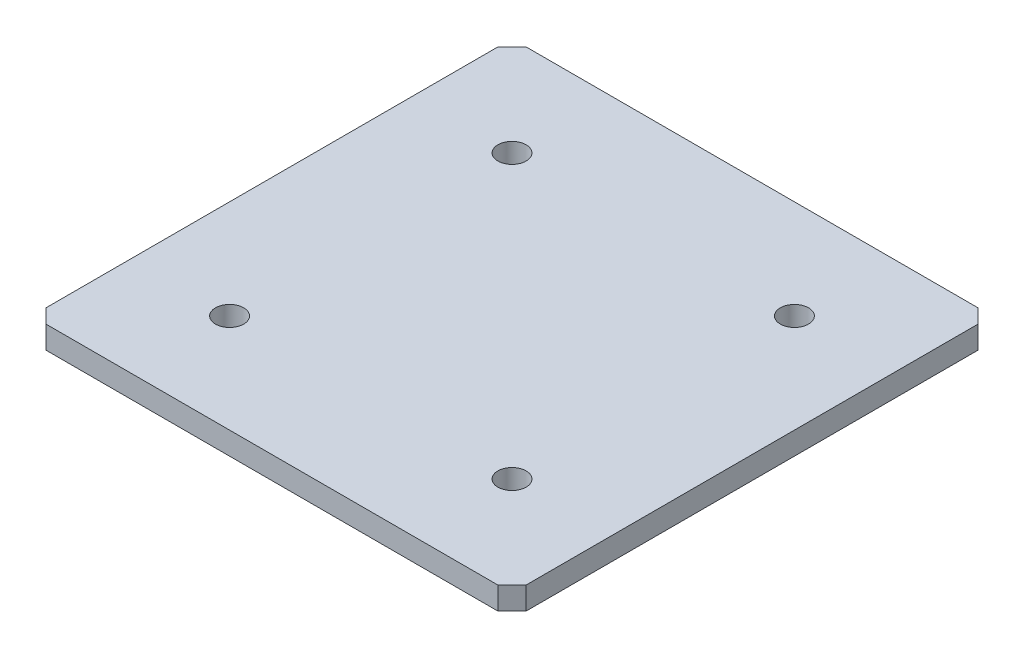
SolidWorks part; units mm, degrees
material "AU4G - 2017A"
ref_plane "Plan de face" through (0, 0, 0) normal (0, 0, 1) x (1, 0, 0)
ref_plane "Plan de dessus" through (0, 0, 0) normal (0, 1, 0) x (1, 0, 0)
ref_plane "Plan de droite" through (0, 0, 0) normal (1, 0, 0) x (0, 0, -1)
sketch "Sketch1" plane through (0, 0, 0) normal (0, 1, 0) x (1, 0, 0)
  line L0 (-85, -85) -> (85, 85) construction
  line L1 (-85, -85) -> (85, -85)
  line L2 (-85, -85) -> (-85, 85)
  line L3 (-85, 85) -> (85, 85)
  line L4 (85, -85) -> (85, 85)
  point P4 (0, 0)
  dimension "D1" = 170
  dimension "D2" = 170
extrude "Boss-Extrude1" add sketch "Sketch1" along normal blind 8
sketch "Sketch2" plane through (0, 8, 0) normal (0, 1, 0) x (1, 0, 0)
  circle A0 centre (0, 0) radius 30.5
  dimension "D1" = 61
sketch "Sketch3" plane through (0, 8, 0) normal (0, 1, 0) x (1, 0, 0)
  line L0 (-85, 0) -> (-89.4469, 0) construction
  line L1 (-85, 85) -> (-85, -85) construction
  line L2 (0, -85) -> (0, -62.1463) construction
  line L3 (-85, -85) -> (85, -85) construction
  circle A0 centre (-50, 50) radius 5
  circle A1 centre (50, 50) radius 5
  circle A2 centre (-50, -50) radius 5
  circle A3 centre (50, -50) radius 5
  dimension "D3" = 10
  dimension "D1" = 100
  dimension "D2" = 100
extrude "Cut-Extrude2" cut sketch "Sketch3" against normal up to next
chamfer "Chamfer1" distance 5 angle 45 4 edges at (-85, 4, -85) (85, 4, -85) (85, 4, 85) (-85, 4, 85)
